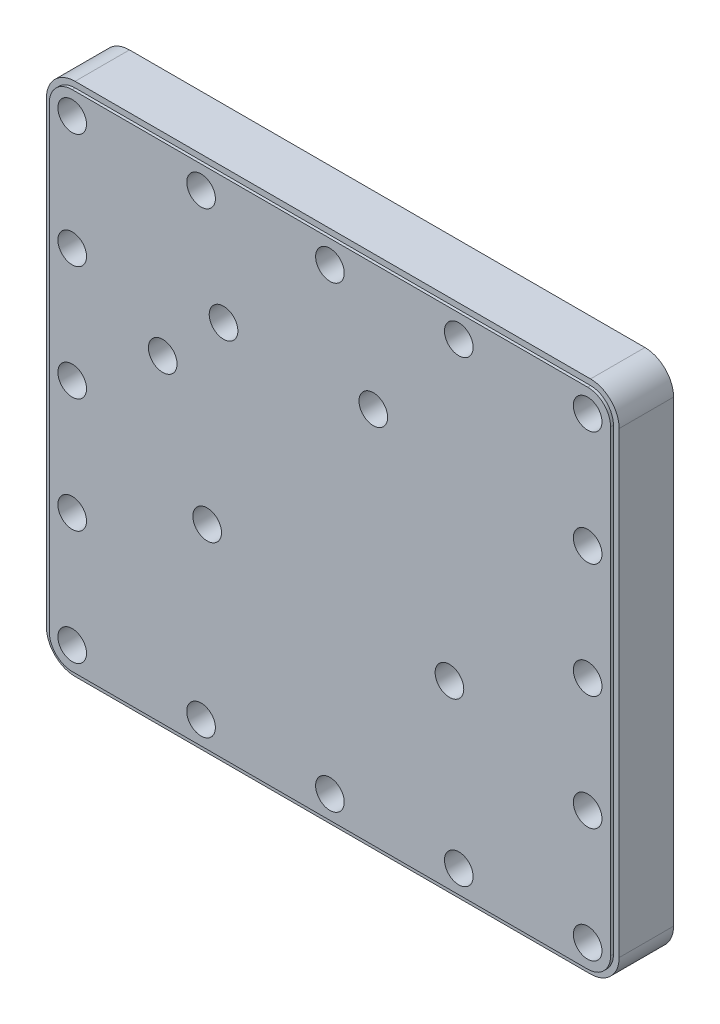
SolidWorks part; units mm, degrees
ref_plane "前视基准面" through (0, 0, 0) normal (0, 0, 1) x (1, 0, 0)
ref_plane "上视基准面" through (0, 0, 0) normal (0, 1, 0) x (1, 0, 0)
ref_plane "右视基准面" through (0, 0, 0) normal (1, 0, 0) x (0, 0, -1)
sketch "草图1" plane through (0, 0, 0) normal (0, 0, 1) x (1, 0, 0)
  line L0 (0, 41.5424) -> (0, -51.1772) construction
  line L1 (-90, -90) -> (90, -90)
  line L2 (-100, -80) -> (-100, 80)
  line L3 (-90, 90) -> (90, 90)
  line L4 (100, -80) -> (100, 80)
  line L5 (-100, -90) -> (100, 90) construction
  line L6 (-100, 90) -> (100, -90) construction
  line L7 (-39.3089, 0) -> (48.7848, 0) construction
  line L8 (90, 80) -> (90, -80) construction
  line L9 (-90, 80) -> (90, 80) construction
  circle A0 centre (-90, 80) radius 5
  circle A1 centre (90, 80) radius 5
  circle A2 centre (90, -80) radius 5
  circle A3 centre (-90, -80) radius 5
  arc A4 (90, 90) -> (100, 80) centre (90, 80) cw
  arc A5 (90, -90) -> (100, -80) centre (90, -80) ccw
  arc A6 (-90, -90) -> (-100, -80) centre (-90, -80) cw
  arc A7 (-100, 80) -> (-90, 90) centre (-90, 80) cw
  circle A8 centre (-37.156, 43.9209) radius 5
  circle A9 centre (15.1451, 43.9209) radius 5
  circle A10 centre (-58.3861, 23.2709) radius 5
  circle A11 centre (-42.8628, -19.9411) radius 5
  circle A12 centre (41.7332, -24.9411) radius 5
  circle A13 centre (90, 0) radius 5
  circle A14 centre (90, 40) radius 5
  circle A15 centre (90, -40) radius 5
  circle A16 centre (-90, -40) radius 5
  circle A17 centre (-90, 0) radius 5
  circle A18 centre (-90, 40) radius 5
  circle A19 centre (0, 80) radius 5
  circle A20 centre (-45, 80) radius 5
  circle A21 centre (45, 80) radius 5
  circle A22 centre (45, -80) radius 5
  circle A23 centre (0, -80) radius 5
  circle A24 centre (-45, -80) radius 5
  point P0 (0, 0)
  dimension "D2" = 10
  dimension "D3" = 10
  dimension "D4" = 10
  dimension "D6" = 10
  dimension "D7" = 10
  dimension "D8" = 10
  dimension "D9" = 10
  dimension "D10" = 10
  dimension "D11" = 10
  dimension "D12" = 10
  dimension "D13" = 10
  dimension "D14" = 40
  dimension "D15" = 40
  dimension "D16" = 10
  dimension "D17" = 10
  dimension "D18" = 45
  dimension "D19" = 45
  dimension "D1" = 180
  dimension "D5" = 200
extrude "凸台-拉伸1" add sketch "草图1" along normal mid plane 20
sketch "草图2" plane through (0, 0, -10) normal (0, 0, -1) x (-1, 0, 0)
  line L1 (-80, -70) -> (80, -70)
  line L2 (-80, -70) -> (-80, 70)
  line L3 (-80, 70) -> (80, 70)
  line L4 (80, -70) -> (80, 70)
  line L5 (-80, -70) -> (80, 70) construction
  line L6 (-80, 70) -> (80, -70) construction
  point P0 (0, 0)
  dimension "D1" = 160
  dimension "D2" = 140
extrude "切除-拉伸1" cut sketch "草图2" against normal blind 1
sketch "草图3" plane through (0, 0, 10) normal (0, 0, 1) x (1, 0, 0)
  line L0 (90, 88) -> (-90, 88)
  line L1 (-98, 80) -> (-98, -80)
  line L2 (-90, -88) -> (90, -88)
  line L3 (98, -80) -> (98, 80)
  line L4 (90, 90) -> (-90, 90)
  line L5 (-100, 80) -> (-100, -80)
  line L6 (-90, -90) -> (90, -90)
  line L7 (100, -80) -> (100, 80)
  line L8 (90, 90) -> (-90, 90)
  line L9 (-100, 80) -> (-100, -80)
  line L10 (-90, -90) -> (90, -90)
  line L11 (100, -80) -> (100, 80)
  arc A0 (-90, 88) -> (-98, 80) centre (-90, 80) ccw
  arc A1 (-98, -80) -> (-90, -88) centre (-90, -80) ccw
  arc A2 (90, -88) -> (98, -80) centre (90, -80) ccw
  arc A3 (98, 80) -> (90, 88) centre (90, 80) ccw
  arc A4 (100, 80) -> (90, 90) centre (90, 80) ccw
  arc A5 (-90, 90) -> (-100, 80) centre (-90, 80) ccw
  arc A6 (-100, -80) -> (-90, -90) centre (-90, -80) ccw
  arc A7 (90, -90) -> (100, -80) centre (90, -80) ccw
  arc A8 (100, 80) -> (90, 90) centre (90, 80) ccw
  arc A9 (-90, 90) -> (-100, 80) centre (-90, 80) ccw
  arc A10 (-100, -80) -> (-90, -90) centre (-90, -80) ccw
  arc A11 (90, -90) -> (100, -80) centre (90, -80) ccw
  dimension "D1" = 0
  dimension "D2" = 2
extrude "切除-拉伸2" cut sketch "草图3" against normal blind 1
